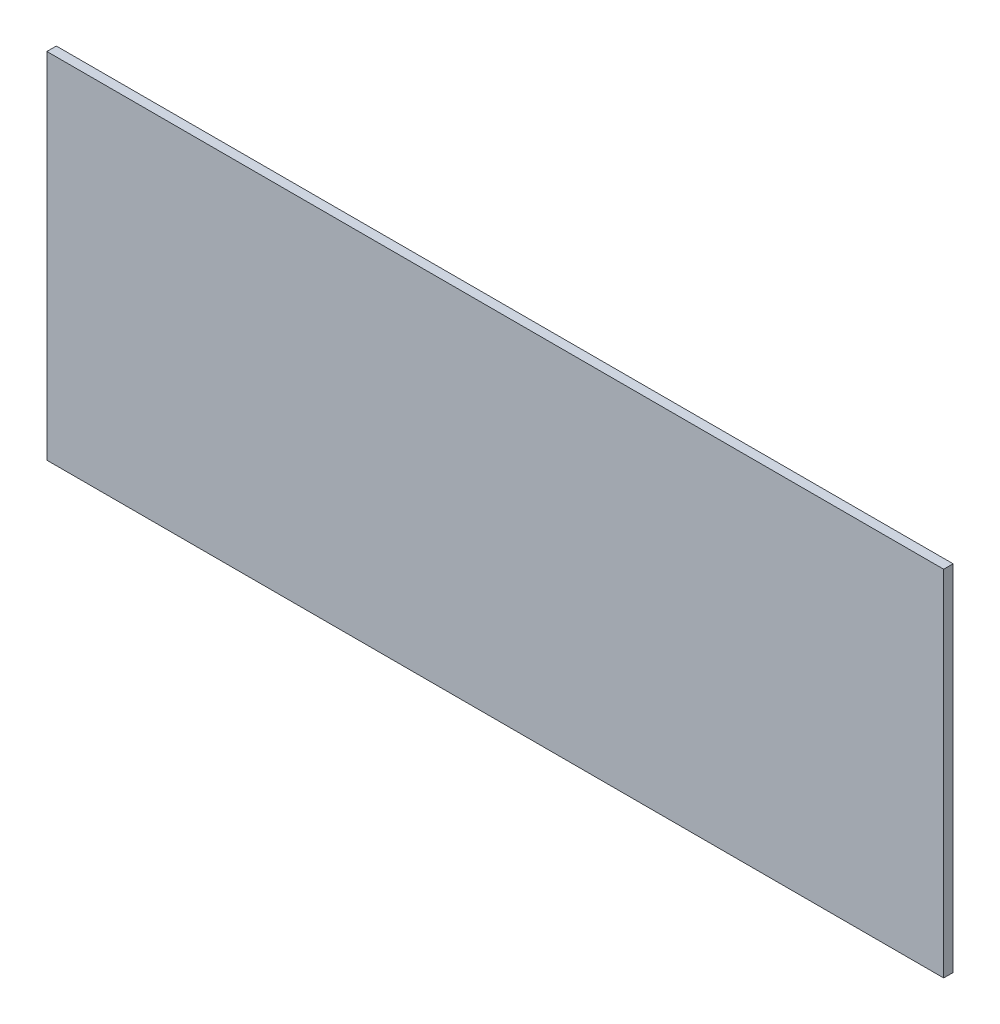
SolidWorks part; units mm, degrees
ref_plane "Plan de face" through (0, 0, 0) normal (0, 0, 1) x (1, 0, 0)
ref_plane "Plan de dessus" through (0, 0, 0) normal (0, 1, 0) x (1, 0, 0)
ref_plane "Plan de droite" through (0, 0, 0) normal (1, 0, 0) x (0, 0, -1)
sketch "Esquisse1" plane through (0, 0, 0) normal (0, 0, 1) x (1, 0, 0)
  line L1 (-191.5313, 22.8927) -> (188.4687, 22.8927)
  line L2 (-191.5313, 22.8927) -> (-191.5313, -127.1073)
  line L3 (-191.5313, -127.1073) -> (188.4687, -127.1073)
  line L4 (188.4687, 22.8927) -> (188.4687, -127.1073)
  dimension "D1" = 380
  dimension "D2" = 150
extrude "Boss.-Extru.1" add sketch "Esquisse1" along normal blind 4
